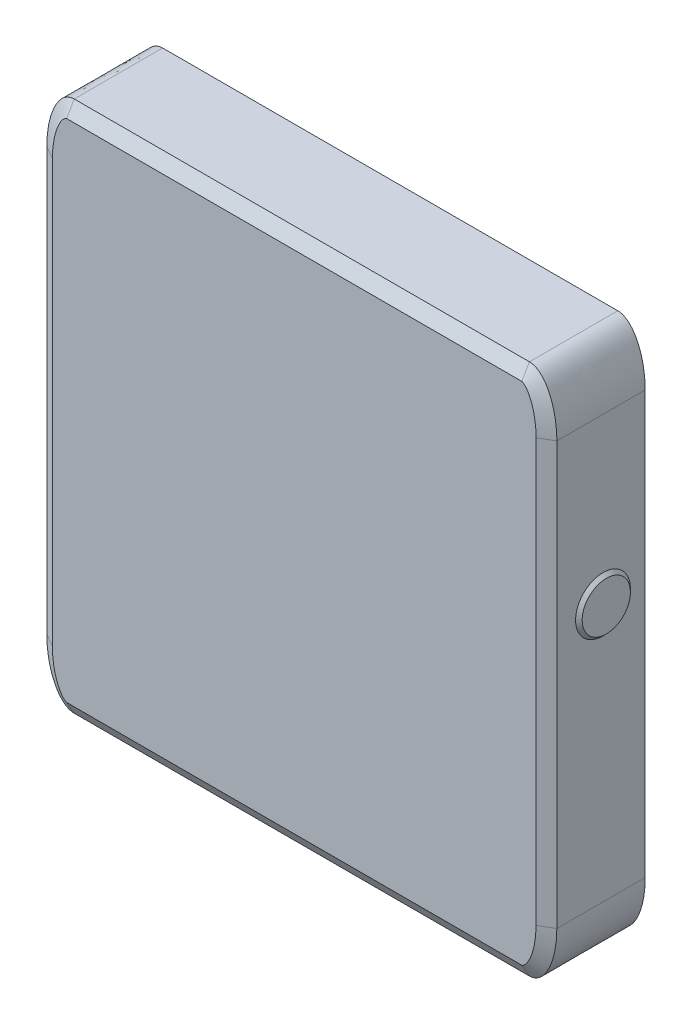
SolidWorks part; units mm, degrees
ref_plane "Front Plane" through (0, 0, 0) normal (0, 0, 1) x (1, 0, 0)
ref_plane "Top Plane" through (0, 0, 0) normal (0, 1, 0) x (1, 0, 0)
ref_plane "Right Plane" through (0, 0, 0) normal (1, 0, 0) x (0, 0, -1)
sketch "Sketch1" plane through (0, 0, 0) normal (0, 0, 1) x (1, 0, 0)
  line L1 (-46.5, 48.5) -> (46.5, 48.5)
  line L2 (-46.5, 48.5) -> (-46.5, -48.5)
  line L3 (-46.5, -48.5) -> (46.5, -48.5)
  line L4 (46.5, 48.5) -> (46.5, -48.5)
  line L5 (-46.5, 48.5) -> (46.5, -48.5) construction
  line L6 (-46.5, -48.5) -> (46.5, 48.5) construction
  point P0 (0, 0)
  dimension "D1" = 93
  dimension "D2" = 97
extrude "Boss-Extrude1" add sketch "Sketch1" along normal blind 17.5
fillet "Fillet1" radius 5 2 edges at (-46.5, 48.5, 8.75) (46.5, -48.5, 8.75) second distance 10 first distance on face at (0, 48.5, 8.75) first distance on face at (0, -48.5, 8.75)
fillet "Fillet2" radius 5 1 edges at (-46.5, -48.5, 8.75) second distance 10 first distance on face at (-24.5, -48.5, 6.5625)
fillet "Fillet3" radius 5 1 edges at (46.5, 48.5, 8.75) second distance 10 first distance on face at (24.5, 48.5, 6.5625)
sketch "Sketch2" plane through (0, -48.5, 0) normal (0, -1, 0) x (1, 0, 0)
  line L5 (-3.67, 10.03) -> (3.67, 10.03)
  line L6 (-3.67, 10.03) -> (-3.67, 7.47)
  line L7 (41.5, 0) -> (41.5, 17.5) construction
  line L8 (41.5, 8.75) -> (0, 8.75) construction
  line L9 (-3.67, 7.47) -> (3.67, 7.47)
  line L10 (3.67, 10.03) -> (3.67, 7.47)
  line L11 (-3.67, 10.03) -> (3.67, 7.47) construction
  line L12 (-3.67, 7.47) -> (3.67, 10.03) construction
  circle A0 centre (-3.67, 8.75) radius 1.28
  circle A1 centre (3.67, 8.75) radius 1.28
  dimension "D1" = 7.34
  dimension "D2" = 2.56
extrude "Cut-Extrude1" cut sketch "Sketch2" against normal blind 11.3 contours A0 | L6 L5 L10 L9 | A1
sketch "Sketch3" plane through (46.5, 0, 0) normal (1, 0, 0) x (0, 0, -1)
  line L0 (-17.5, 48.5) -> (0, 48.5) construction
  line L5 (-17.5, 48.5) -> (0, 48.5)
  line L6 (0, -38.5) -> (0, 38.5) construction
  circle A2 centre (-7.7, 8.5) radius 3.5 construction
  circle A3 centre (-7.7, 8.5) radius 5
  dimension "D1" = 7
  dimension "D3" = 7.7
  dimension "D4" = 10
  dimension "D2" = 40
extrude "Boss-Extrude2" add sketch "Sketch3" along normal blind 0.6 contours A3
chamfer "Chamfer1" distance 0.6 angle 45 1 edges at (47.1, 13.5, 7.7)
sketch "Sketch4" plane through (-46.5, 0, 0) normal (-1, 0, 0) x (0, 0, 1)
  line L0 (0, -55) -> (0, 55) construction
  line L1 (3, 34.5) -> (13.7, 34.5)
  line L2 (2, 33.5) -> (2, 6.8)
  line L3 (3, 5.8) -> (13.7, 5.8)
  line L4 (14.7, 33.5) -> (14.7, 6.8)
  line L5 (2, 34.5) -> (14.7, 5.8) construction
  line L6 (2, 5.8) -> (14.7, 34.5) construction
  line L7 (0, 48.5) -> (17.5, 48.5) construction
  line L8 (0, 48.5) -> (17.5, 48.5)
  arc A0 (13.7, 34.5) -> (14.7, 33.5) centre (13.7, 33.5) cw
  arc A1 (3, 34.5) -> (2, 33.5) centre (3, 33.5) ccw
  arc A2 (2, 6.8) -> (3, 5.8) centre (3, 6.8) ccw
  arc A3 (13.7, 5.8) -> (14.7, 6.8) centre (13.7, 6.8) ccw
  point P0 (8.35, 20.15)
  dimension "D5" = 1
  dimension "D1" = 2
  dimension "D2" = 14
  dimension "D3" = 28.7
  dimension "D4" = 12.7
extrude "Cut-Extrude2" cut sketch "Sketch4" against normal blind 0.2 contours L4 A3 L3 A2 L2 A1 L1 A0
chamfer "Chamfer4" distance 2.4 angle 30 8 edges first distance on face at (0, 0, 17.5)
sketch "Sketch5" plane through (0, 0, 0) normal (0, 0, -1) x (-1, 0, 0)
  line L0 (-41.5, 48.5) -> (41.5, 48.5) construction
  circle A0 centre (0, 29.5) radius 2
  point P4 (2.0336, 29)
  point P5 (0, 29)
  dimension "D1" = 19
  dimension "D2" = 4
extrude "Cut-Extrude3" cut sketch "Sketch5" against normal blind 5 contours A0
equation "\"DisplayHeight\"= 18mm"
equation "\"DisplayWidth\"= 93mm"
equation "\"DisplayTall\"= 97mm"
